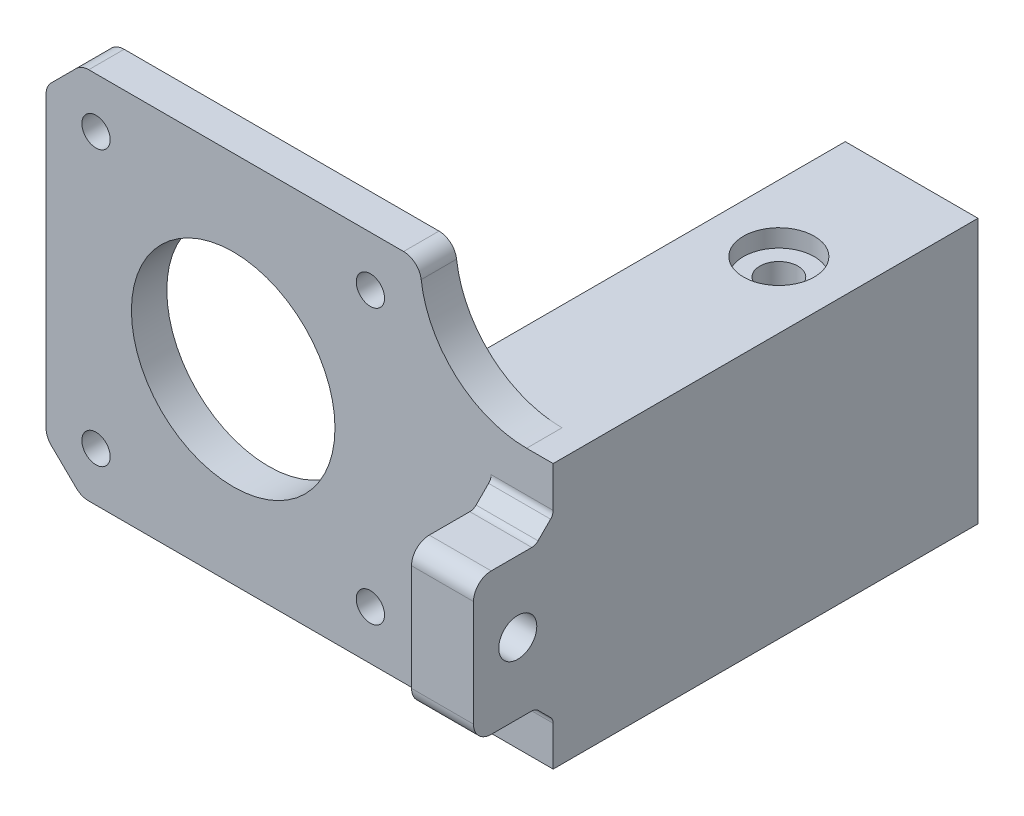
SolidWorks part; units mm, degrees
ref_plane "Front Plane" through (0, 0, 0) normal (0, 0, 1) x (1, 0, 0)
ref_plane "Top Plane" through (0, 0, 0) normal (0, 1, 0) x (1, 0, 0)
ref_plane "Right Plane" through (0, 0, 0) normal (1, 0, 0) x (0, 0, -1)
sketch "Croquis1" plane through (0, 0, 0) normal (0, 0, 1) x (1, 0, 0)
  line L0 (-21.15, 17.15) -> (-17.15, 21.15) construction
  line L1 (-21.15, -17.15) -> (-21.15, 17.15) construction
  line L5 (21.15, 21.15) -> (17.15, 21.15)
  line L14 (-17.15, 21.15) -> (17.15, 21.15) construction
  line L15 (-21.15, 17.15) -> (-17.15, 21.15)
  line L16 (-21.15, -17.15) -> (-21.15, 17.15)
  line L21 (-17.15, 21.15) -> (17.15, 21.15)
  line L24 (36.15, -21.05) -> (36.15, 21.15)
  line L25 (36.15, 21.15) -> (21.15, 21.15)
  line L27 (-17.15, -21.05) -> (-21.15, -17.15)
  line L28 (17.15, -21.05) -> (-17.15, -21.05)
  line L29 (17.15, -21.05) -> (-17.15, -21.05)
  line L30 (17.15, -21.05) -> (36.15, -21.05)
  circle A2 centre (-15.5, 15.5) radius 1.6
  circle A3 centre (-15.5, 15.5) radius 1.6
  circle A5 centre (-15.5, -15.5) radius 1.6
  circle A6 centre (-15.5, -15.5) radius 1.6
  circle A8 centre (15.5, 15.5) radius 1.6
  circle A9 centre (15.5, 15.5) radius 1.6
  circle A10 centre (0, 0) radius 11.5 construction
  circle A11 centre (15.5, -15.5) radius 1.6
  circle A12 centre (15.5, -15.5) radius 1.6
  circle A13 centre (0, 0) radius 11.5
  dimension "D1" = 4
  dimension "D6" = 15
  dimension "D2" = 0.35
  dimension "D3" = 0.35
  dimension "D4" = 0.35
  dimension "D5" = 0.35
  dimension "D7" = 0.1
extrude "Saliente-Extruir1" add sketch "Croquis1" along normal blind 4
sketch "Croquis2" plane through (36.15, 0, 0) normal (1, 0, 0) x (0, 0, -1)
  line L0 (-331, -6.05) -> (-331, -6.25) construction
  line L1 (-331, -6.05) -> (-331, -6.25)
  line L2 (-331, -6.15) -> (216.1427, -6.15) construction
  line L4 (-13, -14.15) -> (-3, -14.15)
  line L5 (-13, -14.15) -> (-13, 1.85)
  line L6 (-13, 1.85) -> (-3, 1.85)
  line L7 (-3, -14.15) -> (-3, 1.85)
  line L8 (-8, 1.85) -> (-8, -14.15) construction
  line L9 (-13, -6.15) -> (-3, -6.15) construction
  circle A0 centre (-8, -6.15) radius 2.15
  point P2 (-331, -6.15)
  point P5 (-8, -6.15)
  dimension "D3" = 4.3
  dimension "D1" = 10
  dimension "D2" = 16
extrude "Saliente-Extruir2" add sketch "Croquis2" against normal blind 7 contours L6 L5 L4 A0 region at (36.15, -6.15, 12.8113)
sketch "Croquis3" plane through (0, 0, 0) normal (0, 0, -1) x (-1, 0, 0)
  line L0 (-21.15, 17.15) -> (-21.15, -17.15) construction
  line L1 (-21.15, 21.15) -> (-21.15, -21.05)
  line L2 (17.15, -21.05) -> (-36.15, -21.05) construction
  line L3 (-21.15, -21.05) -> (-36.15, -21.05)
  line L4 (-36.15, -21.05) -> (-36.15, 21.15)
  line L5 (-36.15, -21.05) -> (-36.15, 21.15) construction
  line L6 (-36.15, 21.15) -> (-21.15, 21.15)
  line L7 (-36.15, 21.15) -> (17.15, 21.15) construction
extrude "Saliente-Extruir3" add sketch "Croquis3" along normal up to surface (44 mm away)
sketch "Croquis4" plane through (0, 21.15, 0) normal (0, 1, 0) x (1, 0, 0)
  line L0 (21.15, 44) -> (21.15, 0) construction
  line L1 (36.15, 44) -> (21.15, 44)
  line L2 (36.15, 44) -> (36.15, -4)
  line L3 (36.15, -4) -> (21.15, -4)
  line L4 (21.15, 44) -> (21.15, -4)
  line L6 (36.15, -4) -> (-17.15, -4) construction
extrude "Cortar-Extruir1" cut sketch "Croquis4" against normal up to surface (12.3 mm away)
fillet "Redondeo1" radius 12 1 edges at (21.15, 8.85, 2)
fillet "Redondeo2" radius 2 1 edges at (21.15, 21.15, 2)
fillet "Redondeo3" radius 2 4 edges at (-17.15, -21.05, 2) (-21.15, -17.15, 2) (-21.15, 17.15, 2) (-17.15, 21.15, 2)
chamfer "Chaflán1" distance 2 1 edges at (32.65, 1.85, 4)
chamfer "Chaflán2" distance 2 1 edges at (32.65, -14.15, 4)
fillet "Redondeo4" radius 2 2 edges at (32.65, -14.15, 13) (32.65, 1.85, 13)
fillet "Redondeo5" radius 1 4 edges at (32.65, -16.15, 4) (32.65, 3.85, 4) (32.65, 1.85, 6) (32.65, -14.15, 6)
sketch "Croquis5" plane through (0, 8.85, 0) normal (0, 1, 0) x (1, 0, 0)
  line L0 (21.15, 44) -> (36.15, 44) construction
  line L1 (21.15, 44) -> (36.15, 44) construction
  line L2 (28.65, 44) -> (28.65, 3.3226) construction
  circle A0 centre (28.65, 29) radius 2.15
  circle A1 centre (28.65, 29) radius 4
  dimension "D1" = 4.3
  dimension "D3" = 8
  dimension "D2" = 15
extrude "Cortar-Extruir2" cut sketch "Croquis5" against normal through all contours A0 region at (28.65, 8.85, -29)
extrude "Cortar-Extruir3" cut sketch "Croquis5<3>" against normal blind 2 contours A1 A0 region at (24.7631, 8.85, -29)
sketch "Croquis5<3>" plane through (0, 8.85, 0) normal (0, 1, 0) x (1, 0, 0) same geometry as "Croquis5"
